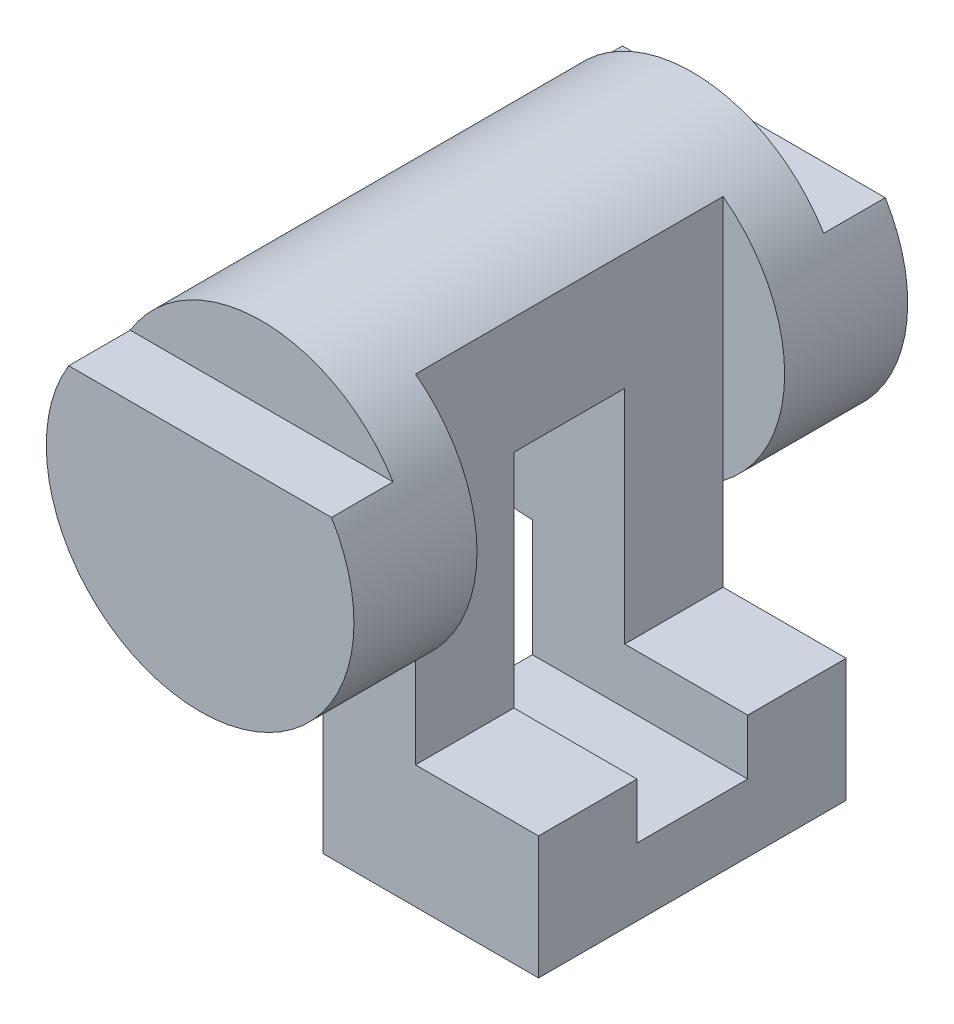
SolidWorks part; units mm, degrees
note: The reader was unsure of these and kept them because the rebuilt part matched: shared geometry of "Croquis2<2>".
ref_plane "Alzado" through (0, 0, 0) normal (0, 0, 1) x (1, 0, 0)
ref_plane "Planta" through (0, 0, 0) normal (0, 1, 0) x (1, 0, 0)
ref_plane "Vista lateral" through (0, 0, 0) normal (1, 0, 0) x (0, 0, -1)
sketch "Croquis1" plane through (0, 0, 0) normal (0, 0, 1) x (1, 0, 0)
  circle A0 centre (0, 0) radius 25
  dimension "D1" = 50
extrude "Saliente-Extruir1" add sketch "Croquis1" along normal mid plane 90
sketch "Croquis2" plane through (0, 0, 45) normal (0, 0, 1) x (1, 0, 0)
  line L0 (-21.3542, 13) -> (21.3542, 13)
  circle A0 centre (0, 0) radius 25 construction
  circle A2 centre (0, 0) radius 25
  arc A3 (21.3542, 13) -> (-21.3542, 13) centre (0, 0) ccw
  point P4 (0, -25)
  dimension "D2" = 38
  dimension "D1" = 0
extrude "Cortar-Extruir1" cut sketch "Croquis2" against normal blind 10
extrude "Cortar-Extruir2" cut sketch "Croquis2<2>" along normal blind 10 from surface at -90
sketch "Croquis2<2>" plane through (0, 0, 45) normal (0, 0, 1) x (1, 0, 0) same geometry as "Croquis2"
ref_plane "Plano1" through (0, -55, 0) normal (0, 1, 0) x (1, 0, 0)
sketch "Croquis3" plane through (0, -55, 0) normal (0, 1, 0) x (1, 0, 0)
  line L1 (0, -25) -> (35, -25)
  line L2 (0, -25) -> (0, 25)
  line L3 (0, 25) -> (35, 25)
  line L4 (35, -25) -> (35, 25)
  point P4 (0, 0)
  dimension "D1" = 50
  dimension "D2" = 35
extrude "Saliente-Extruir2" add sketch "Croquis3" along normal up to vertex (68 mm away)
sketch "Croquis4" plane through (0, 13, 0) normal (0, 1, 0) x (1, 0, 0)
  line L1 (35, -25) -> (15, -25)
  line L2 (35, -25) -> (35, 25)
  line L3 (35, 25) -> (15, 25)
  line L4 (15, -25) -> (15, 25)
  dimension "D1" = 20
extrude "Cortar-Extruir4" cut sketch "Croquis4" against normal offset from surface 20 and the other way through all up to face at (17.5, -55, 0)
sketch "Croquis5" plane through (35, 0, 0) normal (1, 0, 0) x (0, 0, -1)
  line L0 (-25, -35) -> (-25, -55) construction
  line L1 (-9, 1) -> (9, 1)
  line L2 (-9, 1) -> (-9, -44)
  line L3 (-9, -44) -> (9, -44)
  line L4 (9, 1) -> (9, -44)
  line L5 (25, -35) -> (-25, -35) construction
  point P10 (0, -44)
  dimension "D1" = 45
  dimension "D2" = 16
  dimension "D3" = 9
extrude "Cortar-Extruir5" cut sketch "Croquis5" against normal through all
